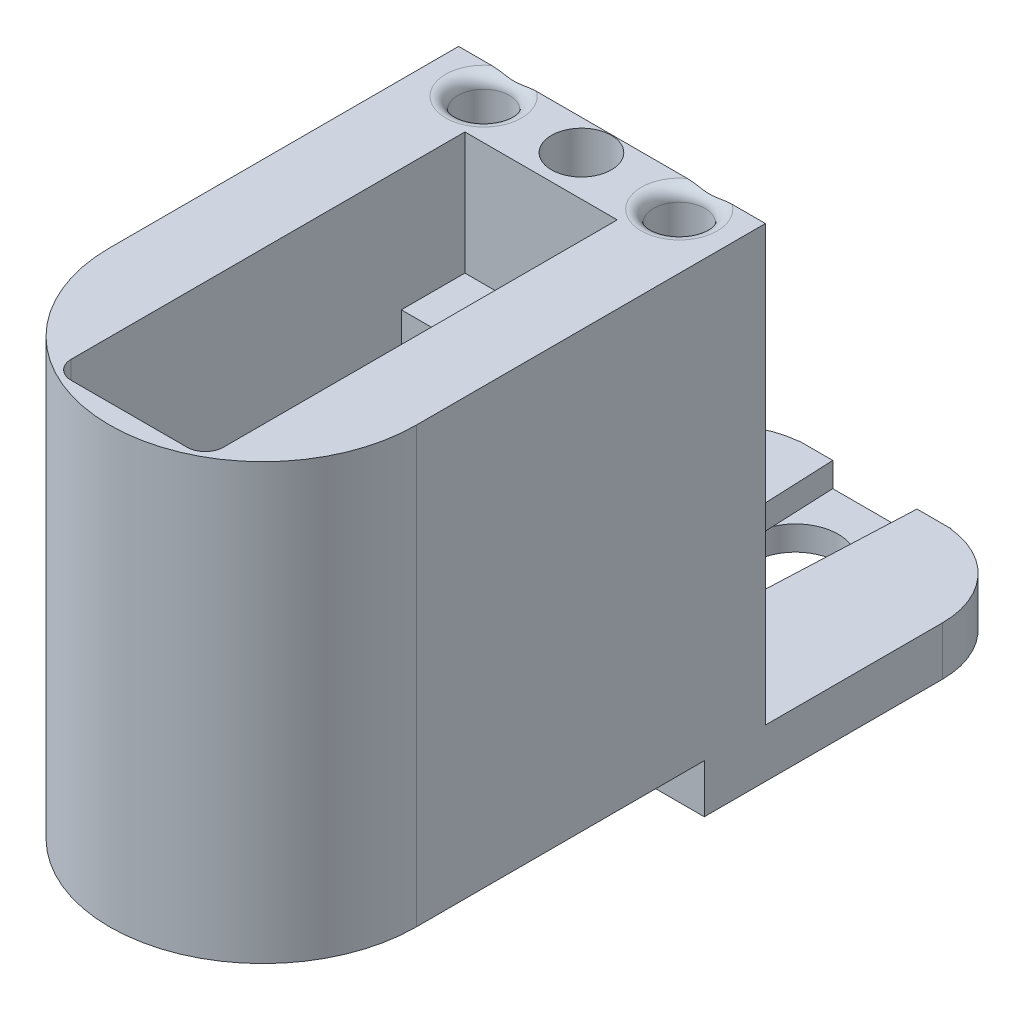
SolidWorks part; units mm, degrees
ref_plane "Front Plane" through (0, 0, 0) normal (0, 0, 1) x (1, 0, 0)
ref_plane "Top Plane" through (0, 0, 0) normal (0, 1, 0) x (1, 0, 0)
ref_plane "Right Plane" through (0, 0, 0) normal (1, 0, 0) x (0, 0, -1)
sketch "Sketch4" plane through (0, 0, 0) normal (0, 0, 1) x (1, 0, 0)
  line L1 (-6.23, -9.975) -> (6.23, -9.975)
  line L2 (-6.23, -9.975) -> (-6.23, 7.275)
  line L3 (-6.23, 7.275) -> (6.23, 7.275)
  line L4 (6.23, -9.975) -> (6.23, 7.275)
  point P4 (0, 7.275)
  dimension "D1" = 12.46
  dimension "D2" = 17.25
  dimension "D3" = 9.975
extrude "Boss-Extrude3" add sketch "Sketch4" along normal blind 6
sketch "Sketch8" plane through (0, -9.975, 0) normal (0, -1, 0) x (-1, 0, 0)
  circle A0 centre (0, -23.55) radius 12.5468
  circle A1 centre (0, -23.55) radius 11.15
  dimension "D1" = 22.3
  dimension "D2" = 23.55
extrude "Boss-Extrude6" add sketch "Sketch8" along normal blind 8.3 and the other way up to surface (17.25 mm away) other way up to face at (0, 7.275, 3)
sketch "Sketch5" plane through (0, 7.275, 0) normal (0, 1, 0) x (1, 0, 0)
  line L8 (12.5468, -23.55) -> (12.5468, 0)
  line L9 (12.5468, 0) -> (6.23, 0)
  line L10 (-12.5468, -23.55) -> (-12.5468, 0)
  line L11 (-12.5468, 0) -> (-6.23, 0)
  line L12 (-6.23, 0) -> (-6.23, -29.7)
  line L14 (6.23, -29.7) -> (6.23, 0)
  line L15 (-6.23, -29.7) -> (6.23, -29.7)
  line L16 (6.23, -6) -> (-6.23, -6) construction
  circle A0 centre (0, -23.55) radius 12.5468 construction
  arc A1 (-12.5468, -23.55) -> (12.5468, -23.55) centre (0, -23.55) ccw
  dimension "D1" = 23.7
  dimension "D2" = 23.55
extrude "Boss-Extrude4" add sketch "Sketch5" against normal up to surface (17.25 mm away) up to face at (0, -9.975, 3)
sketch "Sketch6" plane through (0, 7.275, 0) normal (0, 1, 0) x (1, 0, 0)
  line L0 (6.23, -6) -> (-6.23, -6) construction
  line L3 (6.23, -29.7) -> (-6.23, -29.7) construction
  circle A0 centre (0, -3.6) radius 0.75
  circle A1 centre (0, -32.1) radius 0.75
  dimension "D1" = 1.5
  dimension "D3" = 1.5
  dimension "D2" = 2.4
  dimension "D4" = 2.4
extrude "Cut-Extrude1" cut sketch "Sketch6" against normal blind 5
chamfer "Chamfer1" distance 0.5 angle 60 2 edges at (0, 7.275, 4.35) (0, 7.275, 32.85) first distance on face at (0, 7.275, 4.35)
sketch "Sketch10" plane through (0, 7.275, 0) normal (0, 1, 0) x (1, 0, 0)
  line L1 (-6.23, -6) -> (6.23, -6)
  line L2 (-6.23, -6) -> (-6.23, -29.7)
  line L3 (-6.23, -29.7) -> (6.23, -29.7)
  line L4 (6.23, -6) -> (6.23, -29.7)
extrude "Cut-Extrude3" cut sketch "Sketch10" against normal up to surface (17.25 mm away) up to face at (0, -9.975, 10.3399)
ref_plane "Plane1" through (0, 0, 36.0968) normal (0, 0, 1) x (1, 0, 0)
sketch "Sketch13" plane through (0, -18.275, 0) normal (0, -1, 0) x (1, 0, 0)
  line L0 (-12.5468, 23.55) -> (-12.5468, 0)
  line L1 (-12.5468, 0) -> (12.5468, 0)
  line L2 (12.5468, 0) -> (12.5468, 23.55)
  arc A0 (-12.5468, 23.55) -> (12.5468, 23.55) centre (0, 23.55) ccw
  point P3 (0, 0)
extrude "Boss-Extrude7" add sketch "Sketch13" against normal up to surface (8.3 mm away) up to face at (0, -9.975, 10.3399)
sketch "Sketch15" plane through (0, 7.275, 0) normal (0, 1, 0) x (1, 0, 0)
  line L0 (-12.5468, 0) -> (12.5468, 0)
  line L1 (12.5468, 0) -> (12.5468, -23.55)
  line L2 (-12.5468, 0) -> (-12.5468, -23.55)
  line L3 (6.23, -6) -> (6.23, -29.7) construction
  line L4 (-6.23, -0.8) -> (6.23, -0.8)
  line L5 (-6.23, -0.8) -> (-6.23, -33)
  line L6 (-4.73, -34.5) -> (4.73, -34.5)
  line L7 (6.23, -0.8) -> (6.23, -33)
  arc A0 (-12.5468, -23.55) -> (12.5468, -23.55) centre (0, -23.55) ccw
  circle A1 centre (0, -3.6) radius 0.75 construction
  arc A2 (4.73, -34.5) -> (6.23, -33) centre (4.73, -33) ccw
  arc A3 (-6.23, -33) -> (-4.73, -34.5) centre (-4.73, -33) ccw
  point P15 (0, -0.8)
  dimension "D1" = 0.8
  dimension "D3" = 1.5
  dimension "D2" = 2.8
  dimension "D4" = 0
  dimension "D5" = 34.5
extrude "Boss-Extrude9" add sketch "Sketch15" along normal blind 10
sketch "Sketch20" plane through (0, -18.275, 0) normal (0, -1, 0) x (1, 0, 0)
  circle A0 centre (0, 23.55) radius 7.15
  circle A1 centre (0, 23.55) radius 11.15
  circle A2 centre (0, 23.55) radius 11.15 construction
  dimension "D1" = 14.3
extrude "Boss-Extrude11" add sketch "Sketch20" against normal up to surface (8.3 mm away) up to face at (0, -9.975, 27.1007)
sketch "Sketch21" plane through (0, -18.275, 0) normal (0, -1, 0) x (1, 0, 0)
  circle A0 centre (0, 23.55) radius 7.15
  circle A1 centre (0, 23.55) radius 10.15
  circle A2 centre (0, 23.55) radius 7.15 construction
  dimension "D1" = 20.3
extrude "Cut-Extrude7" cut sketch "Sketch21" against normal blind 1.3
sketch "Sketch11" plane through (0, 0, 29.7) normal (0, 0, 1) x (1, 0, 0)
  line L1 (-5, -9.975) -> (5, -9.975)
  line L2 (-5, -9.975) -> (-5, -11.975)
  line L3 (-5, -11.975) -> (5, -11.975)
  line L4 (5, -9.975) -> (5, -11.975)
  line L5 (3.6469, -9.975) -> (6.23, -9.975) construction
  point P4 (0, -9.975)
  dimension "D1" = 0
  dimension "D2" = 10
  dimension "D3" = 2
extrude "Cut-Extrude4" cut sketch "Sketch11" against normal up to surface (23.7 mm away) up to face at (0, -1.35, 6)
sketch "Sketch24" plane through (0, -18.275, 0) normal (0, -1, 0) x (1, 0, 0)
  line L0 (6.23, 20.0415) -> (6.23, 6) construction
  line L1 (-6.23, 6) -> (6.23, 6)
  line L2 (-6.23, 6) -> (-6.23, 12)
  line L3 (-6.23, 12) -> (6.23, 12)
  line L4 (6.23, 6) -> (6.23, 12)
  dimension "D1" = 6
extrude "Cut-Extrude8" cut sketch "Sketch24" against normal up to next
sketch "Sketch17" plane through (-12.5468, 4.7282, 0) normal (1, 0, 0) x (0, -1, 0)
  line L0 (26.9782, 26.5) -> (26.9782, 0)
  line L1 (26.9782, 0) -> (-17.5218, 0)
  line L2 (-17.5218, 0) -> (-17.5218, 26.5)
  line L3 (-17.5218, 26.5) -> (-13.5218, 26.5)
  line L4 (-13.5218, 26.5) -> (-13.5218, 5)
  line L5 (-13.5218, 5) -> (22.9782, 5)
  line L6 (22.9782, 5) -> (22.9782, 26.5)
  line L7 (22.9782, 26.5) -> (26.9782, 26.5)
  point P2 (4.7282, 5)
  point P10 (4.7282, 0)
  dimension "D1" = 4
  dimension "D2" = 36.5
  dimension "D3" = 0
  dimension "D4" = 26.5
  dimension "D5" = 5
extrude "Boss-Extrude10" add sketch "Sketch17" along normal up to surface (25.0936 mm away) up to face at (12.5468, -0.5, 11.775)
sketch "Sketch18" plane through (0, -18.25, 0) normal (0, 1, 0) x (0, 0, 1)
  line L0 (-26.5, -12.5468) -> (-26.5, 12.5468) construction
  line L1 (-26.5, 6.2191) -> (-5, 6.2191)
  line L2 (-26.5, 6.2191) -> (-26.5, -6.2191)
  line L3 (-26.5, -6.2191) -> (-5, -6.2191)
  line L4 (-5, 6.2191) -> (-5, -6.2191)
  line L5 (-5, -12.5468) -> (-5, 12.5468) construction
  point P6 (-26.5, 0)
  point P7 (-26.5, 0)
  dimension "D1" = 0
extrude "Cut-Extrude5" cut sketch "Sketch18" against normal blind 2
sketch "Sketch19" plane through (0, -20.25, 0) normal (0, 1, 0) x (0, 0, 1)
  line L0 (-26.5, -12.5468) -> (-26.5, 12.5468) construction
  line L1 (-26.5, 12.5468) -> (-26.5, -12.5468) construction
  circle A0 centre (-20, 0) radius 3.5
  point P8 (-26.5, 0)
  dimension "D1" = 7
  dimension "D2" = 6.5
extrude "Cut-Extrude6" cut sketch "Sketch19" against normal through all both and the other way through all
fillet "Fillet1" radius 7 4 edges at (12.5468, -20.25, -26.5) (-12.5468, -20.25, -26.5) (-12.5468, 20.25, -26.5) (12.5468, 20.25, -26.5)
ref_plane "Plane2" through (0, 0, 0) normal (1, 0, 0) x (0, 0, -1)
ref_plane "Plane3" through (0, -0.5, 0) normal (0, -1, 0) x (-1, 0, 0)
sketch "Sketch22" plane through (0, 22.25, 0) normal (0, 1, 0) x (1, 0, 0)
  circle A0 centre (0, 20) radius 6.5
  dimension "D1" = 13
extrude "Boss-Extrude12" add sketch "Sketch22" against normal blind 5
sketch "Sketch23" plane through (0, 17.25, 0) normal (0, -1, 0) x (1, 0, 0)
  circle A0 centre (0, -20) radius 6.075
  dimension "D1" = 12.15
extrude "Boss-Extrude13" add sketch "Sketch23" along normal blind 5
fillet "Fillet2" radius 1 1 edges at (0, 12.25, -26.075)
sketch "Sketch25" plane through (0, -20.25, 0) normal (0, 1, 0) x (1, 0, 0)
  line L0 (-6.2191, 5) -> (-2.5, 5)
  line L1 (12.5468, 5) -> (-12.5468, 5) construction
  line L2 (-2.5, 5) -> (-3.1585, 20)
  line L3 (-3.1585, 20) -> (-3.4438, 26.5)
  line L4 (-3.4438, 26.5) -> (-6.2191, 26.5)
  line L5 (-6.2191, 26.4676) -> (-6.2191, 5) construction
  line L6 (-6.2191, 26.5) -> (-6.2191, 5)
  line L7 (6.2191, 5) -> (2.5, 5)
  line L8 (2.5, 5) -> (3.1585, 20)
  line L9 (3.1585, 20) -> (3.4438, 26.5)
  line L10 (3.4438, 26.5) -> (6.2191, 26.5)
  line L11 (6.2191, 5) -> (6.2191, 26.4676) construction
  line L12 (6.2191, 26.5) -> (6.2191, 5)
  line L13 (0, -23.6775) -> (0, 23.6775) construction
  line L14 (5.5468, 26.5) -> (-5.5468, 26.5) construction
  circle A0 centre (0, 20) radius 3.5 construction
  dimension "D1" = 5
  dimension "D2" = 2.5
  dimension "D3" = 3.1585
  dimension "D4" = 6.317
  dimension "D5" = 0
  dimension "D6" = 0
extrude "Boss-Extrude15" add sketch "Sketch25" along normal up to surface (2 mm away) up to face at (9.7194, -18.25, -14.2975)
sketch "Sketch26" plane through (0, -22.25, 0) normal (0, -1, 0) x (-1, 0, 0)
  line L0 (0, 23.6775) -> (0, -23.6775) construction
  circle A0 centre (0, 10) radius 0.75
  circle A1 centre (0, 20) radius 3.5 construction
  circle A2 centre (0, 13) radius 0.75
  circle A3 centre (0, 7.5) radius 0.75
  dimension "D1" = 1.5
  dimension "D4" = 7
  dimension "D5" = 12.5
  dimension "D2" = 10
  dimension "D3" = 0
extrude "Cut-Extrude9" cut sketch "Sketch26" against normal up to next
sketch "Sketch27" plane through (-12.5468, 0, 0) normal (-1, 0, 0) x (0, 0, 1)
  line L0 (-26.5, 22.25) -> (0, 22.25)
  line L1 (0, 22.25) -> (0, 17.275)
  line L2 (0, 17.275) -> (-10.3619, 17.275)
  line L3 (-10.3619, 17.275) -> (-10.3619, 7.85)
  line L4 (-10.3619, 7.85) -> (-26.5, 7.85)
  line L5 (-26.5, 7.85) -> (-26.5, 22.25)
extrude "Cut-Extrude10" cut sketch "Sketch27" against normal through all
sketch "Sketch28" plane through (0, 17.275, 0) normal (0, 1, 0) x (1, 0, 0)
  line L0 (0, -23.6775) -> (0, 23.6775) construction
  line L2 (-12.5468, 5) -> (12.5468, 5) construction
  circle A0 centre (-8, 2.5) radius 2.1
  circle A1 centre (8, 2.5) radius 2.1
  circle A2 centre (0, 2.5) radius 2.45
  point P6 (0, 0)
  point P7 (0, 0)
  point P12 (-45.8245, 15.934)
  dimension "D1" = 4.2
  dimension "D2" = 4.2
  dimension "D3" = 4.9
  dimension "D4" = 0
  dimension "D5" = 8
  dimension "D6" = 8
  dimension "D7" = 2.5
extrude "Cut-Extrude11" cut sketch "Sketch28" against normal blind 7
fillet "Fillet3" radius 1 2 edges at (8, 17.275, -0.4) (-8, 17.275, -0.4)
